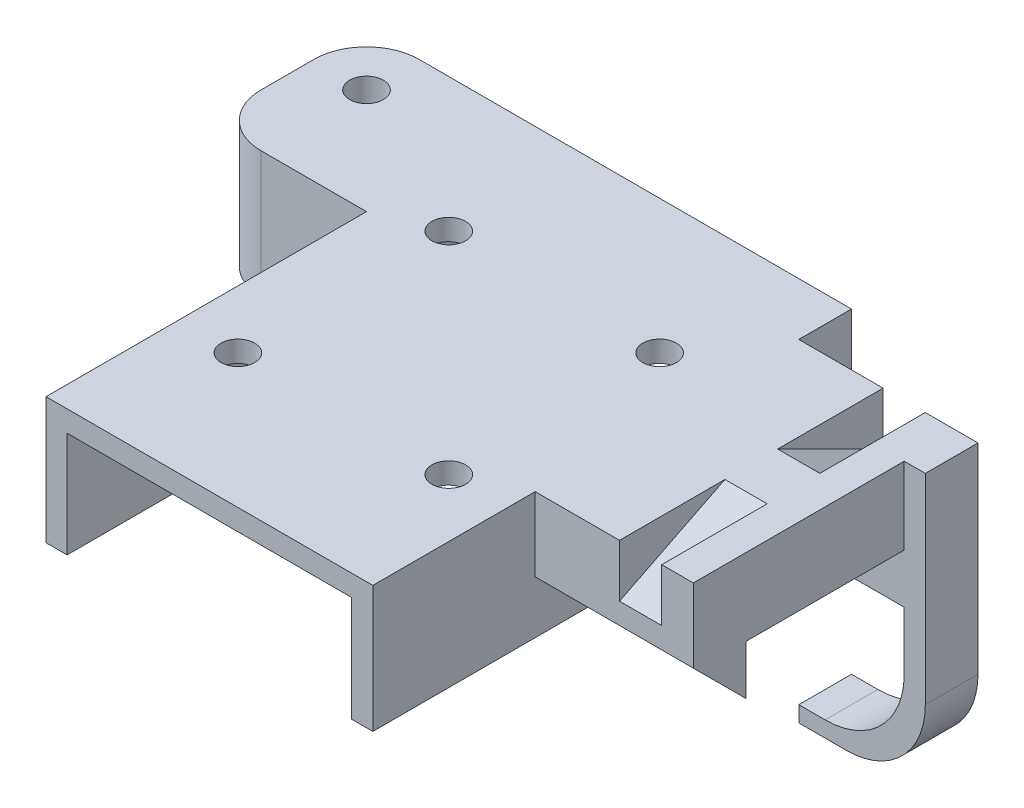
SolidWorks part; units mm, degrees
ref_plane "Front Plane" through (0, 0, 0) normal (0, 0, 1) x (1, 0, 0)
ref_plane "Top Plane" through (0, 0, 0) normal (0, 1, 0) x (1, 0, 0)
ref_plane "Right Plane" through (0, 0, 0) normal (1, 0, 0) x (0, 0, -1)
sketch "Sketch1" plane through (0, 0, 0) normal (0, 1, 0) x (1, 0, 0)
  line L1 (0, 0) -> (31, 0)
  line L2 (0, 0) -> (0, 45.4)
  line L3 (0, 45.4) -> (31, 45.4)
  line L4 (31, 0) -> (31, 45.4)
  dimension "D1" = 31
  dimension "D2" = 45.4
extrude "Boss-Extrude1" add sketch "Sketch1" along normal blind 12
sketch "Sketch2" plane through (0, 0, 0) normal (0, 0, 1) x (1, 0, 0)
  line L0 (0, 0) -> (31, 0) construction
  line L1 (2, 0) -> (29, 0)
  line L2 (2, 0) -> (2, 10)
  line L3 (2, 10) -> (29, 10)
  line L4 (29, 0) -> (29, 10)
  line L5 (0, 12) -> (0, 0) construction
  line L6 (31, 12) -> (31, 0) construction
  dimension "D1" = 2
  dimension "D2" = 2
  dimension "D3" = 10
extrude "Cut-Extrude1" cut sketch "Sketch2" against normal through all
sketch "Sketch3" plane through (0, 12, 0) normal (0, 1, 0) x (1, 0, 0)
  line L0 (15.5, 45.4) -> (15.5, 0) construction
  line L5 (5.5, 12.7) -> (25.5, 12.7) construction
  line L6 (5.5, 12.7) -> (5.5, 32.7) construction
  line L7 (5.5, 32.7) -> (25.5, 32.7) construction
  line L8 (25.5, 12.7) -> (25.5, 32.7) construction
  line L9 (5.5, 12.7) -> (25.5, 32.7) construction
  line L10 (5.5, 32.7) -> (25.5, 12.7) construction
  line L11 (31, 45.4) -> (0, 45.4) construction
  line L12 (0, 0) -> (31, 0) construction
  line L13 (0, 22.7) -> (31, 22.7) construction
  line L14 (0, 45.4) -> (0, 0) construction
  line L15 (31, 0) -> (31, 45.4) construction
  circle A0 centre (5.5, 32.7) radius 1.6
  circle A1 centre (25.5, 32.7) radius 1.6
  circle A2 centre (25.5, 12.7) radius 1.6
  circle A3 centre (5.5, 12.7) radius 1.6
  point P0 (15.5, 22.7)
  dimension "D3" = 3.2
  dimension "D1" = 20
  dimension "D2" = 20
extrude "Cut-Extrude2" cut sketch "Sketch3" against normal blind 10
sketch "Sketch4" plane through (0, 0, 0) normal (-1, 0, 0) x (0, 0, 1)
  line L0 (-45.4, 12) -> (0, 12) construction
  line L1 (-15, 12) -> (0, 12)
  line L2 (-15, 12) -> (-15, 0)
  line L3 (-15, 0) -> (0, 0)
  line L4 (0, 12) -> (0, 0)
  dimension "D1" = 15
extrude "Boss-Extrude2" add sketch "Sketch4" along normal blind 15
sketch "Sketch5" plane through (0, 12, 0) normal (0, 1, 0) x (1, 0, 0)
  line L2 (-15, 0) -> (31, 0) construction
  line L3 (0, 45.4) -> (0, 15) construction
  circle A0 centre (-10, 5) radius 1.6
  dimension "D1" = 3.2
  dimension "D2" = 5
  dimension "D3" = 10
extrude "Cut-Extrude3" cut sketch "Sketch5" against normal blind 20
fillet "Fillet1" radius 5 2 edges at (-15, 6, -15) (-15, 6, 0)
sketch "Sketch6" plane through (31, 0, 0) normal (1, 0, 0) x (0, 0, -1)
  line L9 (5, 0) -> (10, 0)
  line L10 (0, 0) -> (45.4, 0) construction
  line L11 (10, 0) -> (10, 4.7)
  line L12 (10, 4.7) -> (25, 4.7)
  line L13 (25, 4.7) -> (25, 0)
  line L14 (25, 0) -> (30, 0)
  line L15 (30, 0) -> (30, 12)
  line L16 (30, 12) -> (5, 12)
  line L17 (5, 12) -> (5, 0)
  line L18 (0, 12) -> (45.4, 12) construction
  line L19 (0, 12) -> (0, 0) construction
  dimension "D1" = 5
  dimension "D2" = 5
  dimension "D3" = 4.7
  dimension "D4" = 15
  dimension "D5" = 5
extrude "Boss-Extrude3" add sketch "Sketch6" along normal blind 15
chamfer "Chamfer1" distance 5 angle 45 2 edges at (38.5, 0, -5) (38.5, 0, -30)
ref_plane "Plane1" through (43, 0, 0) normal (1, 0, 0) x (0, 0, -1)
sketch "Sketch7" plane through (43, 0, 0) normal (1, 0, 0) x (0, 0, -1)
  line L0 (5, 7) -> (15, 12)
  line L1 (5, 12) -> (5, 5) construction
  line L3 (15, 12) -> (5, 12)
  line L4 (5, 12) -> (5, 7)
  line L5 (30, 7) -> (20, 12)
  line L6 (30, 5) -> (30, 12) construction
  line L7 (20, 12) -> (30, 12)
  line L8 (30, 12) -> (30, 7)
  line L9 (30, 12) -> (5, 12) construction
  point P4 (15, 12)
  dimension "D1" = 5
  dimension "D2" = 5
  dimension "D3" = 10
  dimension "D4" = 10
extrude "Cut-Extrude4" cut sketch "Sketch7" against normal blind 4
mirror "Mirror1" [suppressed] of bodies 111 105
delete or keep bodies "Body-Delete/Keep 1" [suppressed] type delete bodies bodies 111
mirror "Mirror2" [suppressed] of bodies 105
mirror "Mirror3" [suppressed] of bodies 107
delete or keep bodies "Body-Delete/Keep 2" [suppressed] type delete bodies bodies 105 107
mirror "Mirror4" about plane through (0, 12, -45.4) normal (0, 0, 1) of bodies 111 105
delete or keep bodies "Body-Delete/Keep 3" type delete bodies bodies 111
sketch "Sketch10" plane through (46, 0, 0) normal (1, 0, 0) x (0, 0, -1)
  line L0 (60.8, 12) -> (85.8, 12) construction
  line L1 (80.8, 12) -> (85.8, 12)
  line L2 (80.8, 12) -> (80.8, -14.5)
  line L3 (80.8, -14.5) -> (85.8, -14.5)
  line L4 (85.8, 12) -> (85.8, -14.5)
  line L5 (80.8, 0) -> (80.8, 4.7) construction
  line L6 (85.8, 12) -> (85.8, 5) construction
  dimension "D1" = 26.5
extrude "Boss-Extrude7" add sketch "Sketch10" along normal blind 2
sketch "Sketch11" plane through (46, 0, 0) normal (-1, 0, 0) x (0, 0, 1)
  line L0 (-80.8, 0) -> (-80.8, -14.5) construction
  line L1 (-85.8, -14.5) -> (-80.8, -14.5)
  line L2 (-85.8, -14.5) -> (-85.8, -13)
  line L3 (-85.8, -13) -> (-80.8, -13)
  line L4 (-80.8, -14.5) -> (-80.8, -13)
  dimension "D1" = 1.5
extrude "Boss-Extrude8" add sketch "Sketch11" along normal blind 10
fillet "Fillet2" radius 7.5 2 edges at (46, -13, -83.3) (48, -14.5, -83.3)
